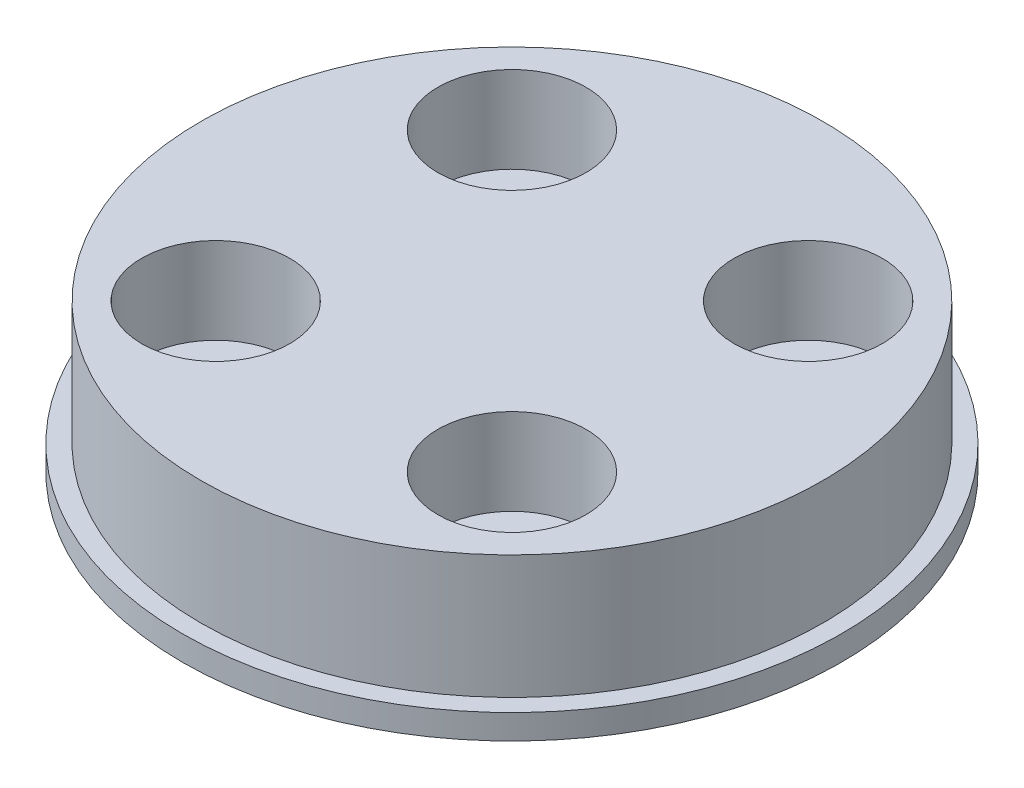
SolidWorks part; units mm, degrees
material "ABS"
ref_plane "Front Plane" through (0, 0, 0) normal (0, 0, 1) x (1, 0, 0)
ref_plane "Top Plane" through (0, 0, 0) normal (0, 1, 0) x (1, 0, 0)
ref_plane "Right Plane" through (0, 0, 0) normal (1, 0, 0) x (0, 0, -1)
sketch "Sketch1" plane through (0, 33, 0) normal (0, 1, 0) x (1, 0, 0)
  circle A0 centre (0, 0) radius 12.6
  circle A1 centre (0, 0) radius 13.35
  circle A2 centre (-6, 6) radius 1.575
  circle A3 centre (6, 6) radius 1.575
  circle A4 centre (6, -6) radius 1.575
  circle A5 centre (-6, -6) radius 1.575
  point P16 (0, 0)
  circle M2 centre (-6, -6) radius 1.575
  circle M3 centre (6, -6) radius 1.575
  circle M4 centre (6, 6) radius 1.575
  circle M5 centre (-6, 6) radius 1.575
  dimension "D1" = 3.15
  dimension "D3" = 25.2
  dimension "D4" = 26.7
  dimension "D2" = 4
extrude "Boss-Extrude1" add sketch "Sketch1" along normal blind 1 contours A0 M3 M5 M4 M2 | A1 A0 region at (0, 33, 0) region at (-12.9724, 33, 0)
extrude "Boss-Extrude2" add sketch "Sketch1<3>" along normal blind 6 contours A0 M3 M5 M4 M2 region at (0, 33, 0)
sketch "Sketch1<3>" plane through (0, 33, 0) normal (0, 1, 0) x (1, 0, 0) same geometry as "Sketch1"
sketch "Sketch2" plane through (0, 39, 0) normal (0, 1, 0) x (1, 0, 0)
  circle A0 centre (-6, 6) radius 3
  circle A1 centre (6, 6) radius 3
  circle A2 centre (6, -6) radius 3
  circle A3 centre (-6, -6) radius 3
  point P12 (0, 0)
  dimension "D1" = 6
  dimension "D2" = 4
extrude "Cut-Extrude1" cut sketch "Sketch2" against normal blind 3.5
equation "\"RingPinShaft\"= 5.05"
equation "\"CenterBearingOut\"=32.00"
equation "\"OutputBearingOut\"=50.00"
equation "\"RingPostIn\"=5.15"
equation "\"CamBearingOut\"=15.1"
equation "\"DiskOutputShaft\"=10.1"
equation "\"CenterShaft\"=25.2"
equation "\"Eccentricity\"=2"
equation "\"CycCamShaft\"=10.05"
equation "\"m3Thru\"=3.15"
equation "\"m3Insert\"=4.2"
equation "\"D1@Sketch1\"=\"m3Thru\""
equation "\"D3@Sketch1\"=\"CenterShaft\""
equation "\"D4@Sketch1\"=\"CenterShaft\"+1.5"
